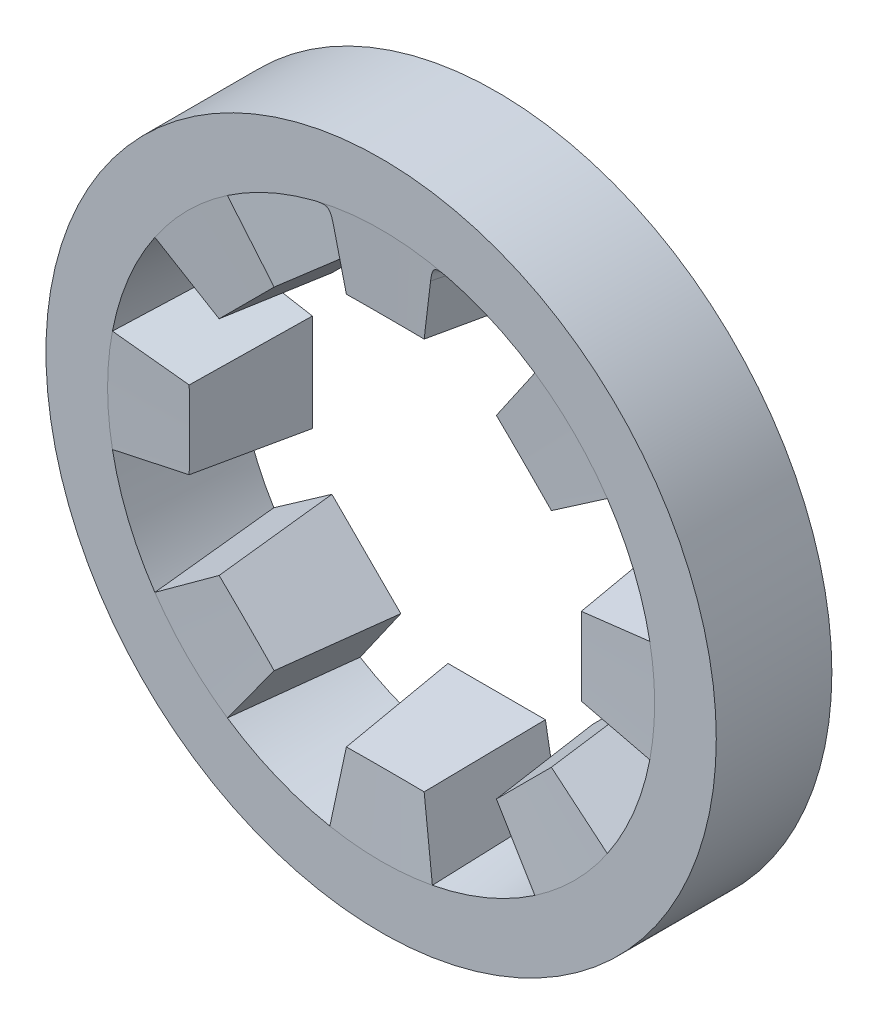
SolidWorks part; units mm, degrees
ref_plane "Front Plane" through (0, 0, 0) normal (0, 0, 1) x (1, 0, 0)
ref_plane "Top Plane" through (0, 0, 0) normal (0, 1, 0) x (1, 0, 0)
ref_plane "Right Plane" through (0, 0, 0) normal (1, 0, 0) x (0, 0, -1)
sketch "Sketch1" plane through (0, 0, 0) normal (0, 0, 1) x (1, 0, 0)
  circle A0 centre (0, 0) radius 21.75
  dimension "D1" = 43.5
extrude "Boss-Extrude1" add sketch "Sketch1" along normal blind 7.5
sketch "Sketch2" plane through (0, 0, 7.5) normal (0, 0, 1) x (1, 0, 0)
  line L0 (-2.5, 12.75) -> (2.5, 12.75)
  line L1 (0, 0) -> (0, 22.5506) construction
  line L2 (2.5, 12.75) -> (3.3262, 17.4356)
  line L3 (-2.5, 12.75) -> (-3.3262, 17.4356)
  line L4 (7.2478, 10.7834) -> (10.7834, 7.2478)
  line L5 (10.7834, 7.2478) -> (14.6808, 9.9768)
  line L6 (7.2478, 10.7834) -> (9.9768, 14.6808)
  line L7 (12.75, 2.5) -> (12.75, -2.5)
  line L8 (12.75, -2.5) -> (17.4356, -3.3262)
  line L9 (12.75, 2.5) -> (17.4356, 3.3262)
  line L10 (10.7834, -7.2478) -> (7.2478, -10.7834)
  line L11 (7.2478, -10.7834) -> (9.9768, -14.6808)
  line L12 (10.7834, -7.2478) -> (14.6808, -9.9768)
  line L13 (2.5, -12.75) -> (-2.5, -12.75)
  line L14 (-2.5, -12.75) -> (-3.3262, -17.4356)
  line L15 (2.5, -12.75) -> (3.3262, -17.4356)
  line L16 (-7.2478, -10.7834) -> (-10.7834, -7.2478)
  line L17 (-10.7834, -7.2478) -> (-14.6808, -9.9768)
  line L18 (-7.2478, -10.7834) -> (-9.9768, -14.6808)
  line L19 (-12.75, -2.5) -> (-12.75, 2.5)
  line L20 (-12.75, 2.5) -> (-17.4356, 3.3262)
  line L21 (-12.75, -2.5) -> (-17.4356, -3.3262)
  line L22 (-10.7834, 7.2478) -> (-7.2478, 10.7834)
  line L23 (-7.2478, 10.7834) -> (-9.9768, 14.6808)
  line L24 (-10.7834, 7.2478) -> (-14.6808, 9.9768)
  circle A0 centre (0, 0) radius 17.75
  circle A1 centre (0, 0) radius 21.75 construction
  point P9 (0, 0)
  point P12 (0, 17.75)
  point P30 (0, 0)
  point P44 (0, 0)
  dimension "D1" = 4
  dimension "D2" = 5
  dimension "D3" = 8
  dimension "D4" = 100
  dimension "D6" = 5
extrude "Cut-Extrude1" cut sketch "Sketch2" against normal blind 11 draft 6 contours A0 L2 L0 L3 region at (0, 0, 7.5)
sketch "Sketch3" plane through (0, 0, 0) normal (1, 0, 0) x (0, 0, -1)
  line L0 (7.9001, 0) -> (-24.9056, 0) construction
  line L1 (-22.7611, 17.75) -> (13.928, 17.75) construction
  line L2 (0, 21.75) -> (-22.1815, 21.75) construction
  line L3 (0, -21.75) -> (0, 21.75) construction
  line L4 (-7.5, 17.75) -> (-6.5, 0)
  line L5 (-7.5, 21.75) -> (-7.5, -21.75) construction
  line L6 (-6.5, 0) -> (-7.5, 0)
  line L7 (-7.5, 0) -> (-7.5, 17.75)
  dimension "D1" = 4
  dimension "D2" = 1
revolve "Cut-Revolve1" cut sketch "Sketch3" angle 360 about L0
fillet "Fillet1" radius 1 2 edges conic rho 0.65
sketch "Sketch4" plane through (0, 0, 7.5) normal (0, 0, 1) x (1, 0, 0)
  circle A0 centre (0, 0) radius 21.75 construction
  point P0 (-21.75, 0)
sketch "Sketch5" plane through (0, 0, 0) normal (0, 0, -1) x (-1, 0, 0)
  circle A0 centre (0, 15.539) radius 2.5
extrude "Cut-Extrude2" cut sketch "Sketch5" against normal blind 5
sketch "Sketch6" plane through (0, 0, 0) normal (0, 0, -1) x (-1, 0, 0)
  circle A0 centre (0, 15.539) radius 3
  point P0 (0, 15.539)
extrude "Cut-Extrude3" cut sketch "Sketch6" against normal blind 1.5
pattern_circular "CirPattern1" count 8 over 360 about axis through (0, 0, 0) along (0, 0, 1) of "Cut-Extrude2", "Cut-Extrude3"
